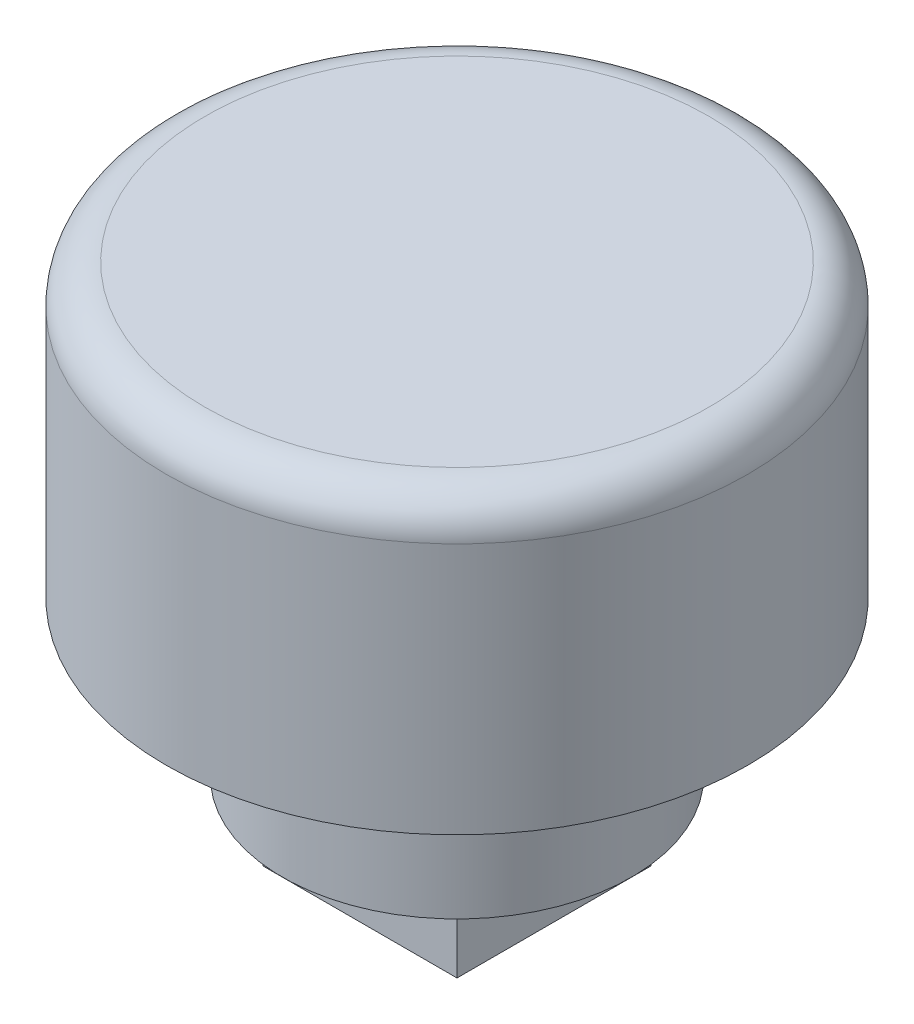
SolidWorks part; units mm, degrees
ref_plane "Front Plane" through (0, 0, 0) normal (0, 0, 1) x (1, 0, 0)
ref_plane "Top Plane" through (0, 0, 0) normal (0, 1, 0) x (1, 0, 0)
ref_plane "Right Plane" through (0, 0, 0) normal (1, 0, 0) x (0, 0, -1)
sketch "Sketch1" plane through (0, 0, 0) normal (0, 1, 0) x (1, 0, 0)
  circle A0 centre (0, 0) radius 7.5
  dimension "D1" = 15
extrude "Boss-Extrude1" add sketch "Sketch1" along normal blind 7.5
fillet "Fillet1" radius 1 1 edges at (0, 7.5, 7.5)
sketch "Sketch2" plane through (0, 0, 0) normal (0, -1, 0) x (-1, 0, 0)
  circle A0 centre (0, 0) radius 4.5
  dimension "D1" = 9
extrude "Boss-Extrude2" add sketch "Sketch2" along normal blind 4
sketch "Sketch3" plane through (0, -4, 0) normal (0, -1, 0) x (-1, 0, 0)
  line L1 (-2.5, 2.5) -> (2.5, 2.5)
  line L2 (-2.5, 2.5) -> (-2.5, -2.5)
  line L3 (-2.5, -2.5) -> (2.5, -2.5)
  line L4 (2.5, 2.5) -> (2.5, -2.5)
  line L5 (-2.5, 2.5) -> (2.5, -2.5) construction
  line L6 (-2.5, -2.5) -> (2.5, 2.5) construction
  point P0 (0, 0)
  dimension "D1" = 5
  dimension "D2" = 5
extrude "Boss-Extrude3" add sketch "Sketch3" along normal blind 2
